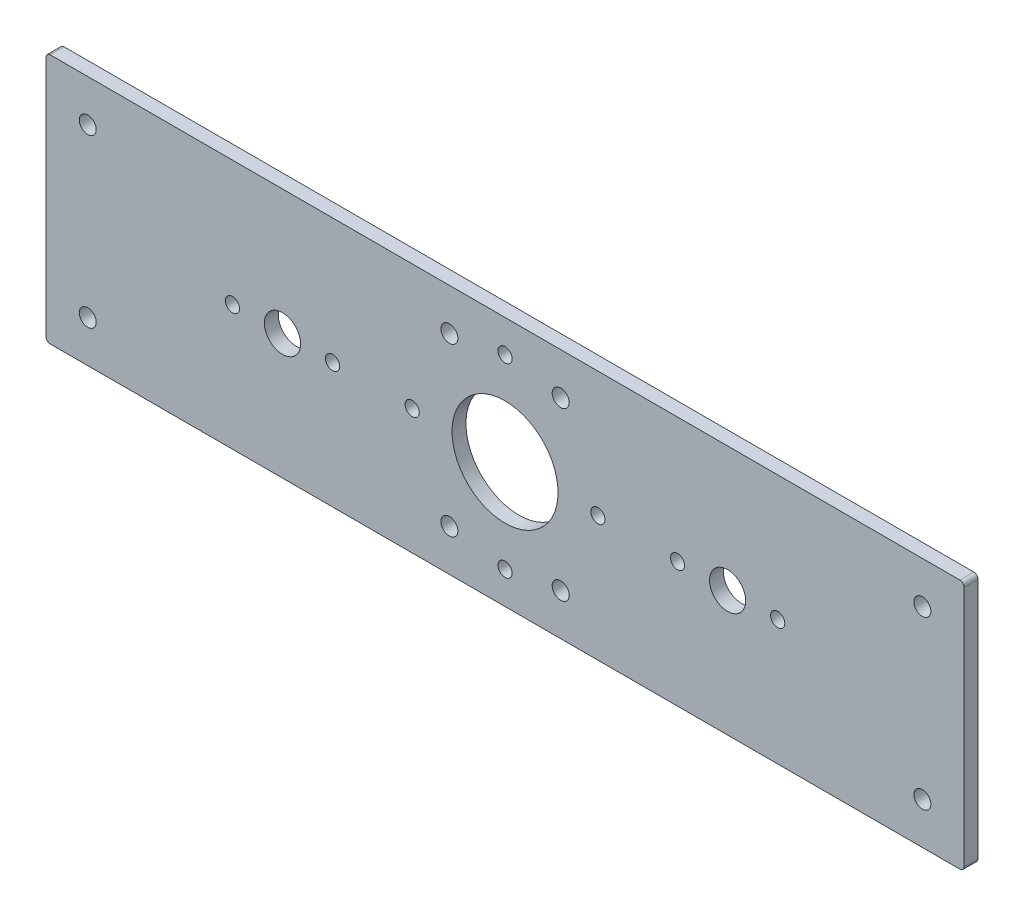
SolidWorks part; units mm, degrees
ref_plane "Front Plane" through (0, 0, 0) normal (0, 0, 1) x (1, 0, 0)
ref_plane "Top Plane" through (0, 0, 0) normal (0, 1, 0) x (1, 0, 0)
ref_plane "Right Plane" through (0, 0, 0) normal (1, 0, 0) x (0, 0, -1)
sketch "Sketch1" plane through (0, 0, 0) normal (0, 0, 1) x (1, 0, 0)
  line L0 (-165, 0) -> (165, 0) construction
  line L1 (165, -45) -> (-165, -45)
  line L2 (165, -45) -> (165, 45)
  line L3 (165, 45) -> (-165, 45)
  line L4 (-165, -45) -> (-165, 45)
  line L5 (165, -45) -> (-165, 45) construction
  line L6 (165, 45) -> (-165, -45) construction
  line L8 (0, -33.3754) -> (33.3754, 0) construction
  line L9 (0, -33.3754) -> (-33.3754, 0) construction
  line L10 (-33.3754, 0) -> (0, 33.3754) construction
  line L11 (33.3754, 0) -> (0, 33.3754) construction
  line L12 (0, -33.3754) -> (0, 33.3754) construction
  line L13 (-33.3754, 0) -> (33.3754, 0) construction
  circle A0 centre (0, 0) radius 19.05
  circle A1 centre (-33.3754, 0) radius 2.55
  circle A2 centre (33.3754, 0) radius 2.55
  circle A3 centre (0, 33.3754) radius 2.55
  circle A4 centre (0, -33.3754) radius 2.55
  point P0 (0, 0)
  dimension "D3" = 38.1
  dimension "D4" = 47.2
  dimension "D5" = 47.2
  dimension "D8" = 5.1
  dimension "D9" = 5.1
  dimension "D10" = 5.1
  dimension "D11" = 5.1
  dimension "D1" = 90
  dimension "D2" = 330
  dimension "D6" = 90
  dimension "D7" = 90
extrude "Boss-Extrude1" add sketch "Sketch1" along normal mid plane 5
sketch "Sketch2" plane through (0, 0, 2.5) normal (0, 0, 1) x (1, 0, 0)
  line L2 (-150, 45) -> (-150, -45)
  line L3 (-150, 45) -> (-150, -45) construction
  line L5 (150, -45) -> (150, 45)
  line L6 (150, -45) -> (150, 45) construction
  line L23 (165, 30) -> (-165, 30)
  line L24 (165, 30) -> (-165, 30) construction
  line L25 (0, 45) -> (0, -45) construction
  line L26 (-165, -30) -> (165, -30)
  line L27 (-165, -30) -> (165, -30) construction
  line L28 (165, 45) -> (-165, 45) construction
  line L29 (-165, -45) -> (165, -45) construction
  line L30 (-20, 45) -> (-20, -45) construction
  line L31 (20, 45) -> (20, -45) construction
  circle A0 centre (-150, 30) radius 3.05
  circle A1 centre (-150, -30) radius 3.05
  circle A2 centre (-20, 30) radius 3.05
  circle A3 centre (-20, -30) radius 3.05
  circle A4 centre (20, -30) radius 3.05
  circle A5 centre (20, 30) radius 3.05
  circle A6 centre (150, 30) radius 3.05
  circle A7 centre (150, -30) radius 3.05
  dimension "D7" = 6.1
  dimension "D8" = 6.1
  dimension "D9" = 6.1
  dimension "D10" = 6.1
  dimension "D11" = 6.1
  dimension "D12" = 6.1
  dimension "D13" = 6.1
  dimension "D14" = 6.1
  dimension "D1" = 15
  dimension "D2" = 15
  dimension "D3" = 15
  dimension "D4" = 15
  dimension "D5" = 20
  dimension "D6" = 20
extrude "Cut-Extrude1" cut sketch "Sketch2" against normal through all
sketch "Sketch3" plane through (0, 0, 2.5) normal (0, 0, 1) x (1, 0, 0)
  line L0 (0, 0) -> (-49.4534, 0) construction
  circle A0 centre (-62, 0) radius 2.55
  circle A1 centre (-98, 0) radius 2.55
  circle A2 centre (-80, 0) radius 6.5
  dimension "D1" = 5.1
  dimension "D2" = 5.1
  dimension "D3" = 13
  dimension "D4" = 80
  dimension "D5" = 18
  dimension "D6" = 18
extrude "Cut-Extrude2" cut sketch "Sketch3" against normal through all
mirror "Mirror1" about plane through (0, 0, 0) normal (1, 0, 0) of "Cut-Extrude2"
fillet "Fillet1" radius 1.5 4 edges at (-165, -45, 0) (165, -45, 0) (165, 45, 0) (-165, 45, 0)
equation "\"D4@Sketch3\"=160/2"
equation "\"D9@Sketch2\"=\"D7@Sketch2\""
equation "\"D12@Sketch2\"=\"D7@Sketch2\""
equation "\"D13@Sketch2\"=\"D7@Sketch2\""
equation "\"D8@Sketch2\"=\"D7@Sketch2\""
equation "\"D10@Sketch2\"=\"D7@Sketch2\""
equation "\"D11@Sketch2\"=\"D7@Sketch2\""
equation "\"D14@Sketch2\"=\"D7@Sketch2\""
equation "\"D9@Sketch1\"=\"D8@Sketch1\""
equation "\"D10@Sketch1\"=\"D8@Sketch1\""
equation "\"D11@Sketch1\"=\"D8@Sketch1\""
